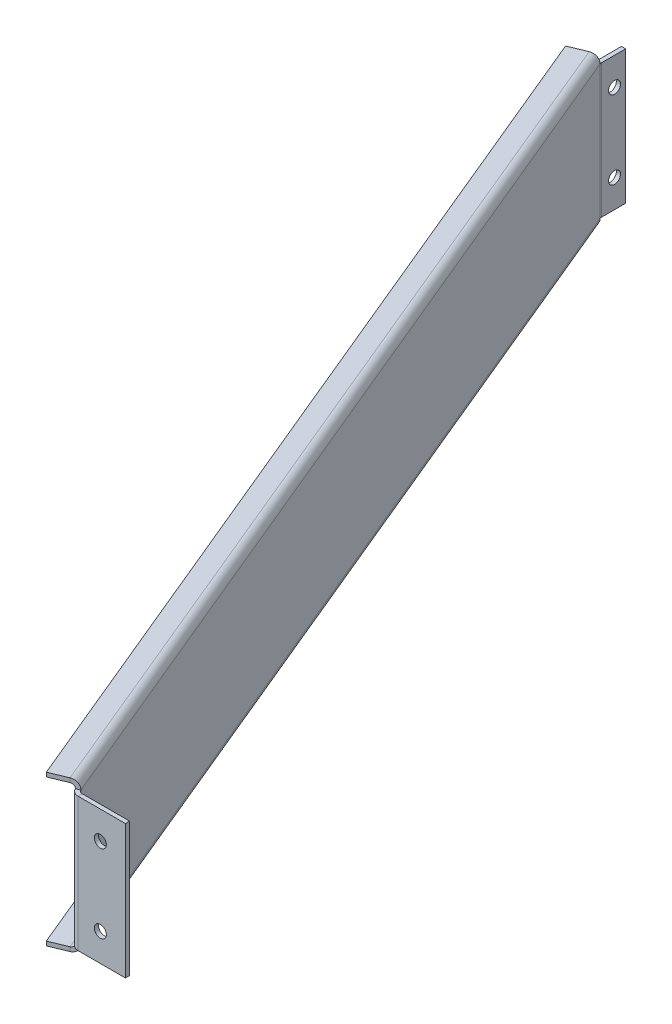
SolidWorks part; units mm, degrees
note: '?' marks a value the reader was unsure of. The reader was unsure of these and kept them because the rebuilt part matched: bend radius of "基体折弯1", "基体折弯2"; flange length of "边线-法兰1".
material "镀铬不锈钢"
ref_plane "前视基准面" through (0, 0, 0) normal (0, 0, 1) x (1, 0, 0)
ref_plane "上视基准面" through (0, 0, 0) normal (0, 1, 0) x (1, 0, 0)
ref_plane "右视基准面" through (0, 0, 0) normal (1, 0, 0) x (0, 0, -1)
ref_axis "基准轴1" through (0, 0, 35.3) along (0, 0, -1)?
sketch "草图1" plane through (0, 0, 0) normal (0, 1, 0) x (1, 0, 0)
  line L0 (63, 329) -> (63, 320)
  line L1 (63, 320) -> (196, 0)
  line L2 (196, 0) -> (214, 0)
  line L3 (0, 0) -> (0, 458.6201) construction
  dimension "D1" = 320
  dimension "D2" = 9
  dimension "D3" = 196
  dimension "D4" = 63
  dimension "D5" = 18
base flange "基体-法兰1" sketch "草图1" end condition mid plane depth 48 reverse direction no thickness 1.5 reverse thickness direction no bend radius 1.5
bend "基体折弯1" bend radius 1.5 bend angle 67.431 parameters "D5"=1
bend "基体折弯2" bend radius 1.5 bend angle 22.569 parameters "D5"=2
edge flange "边线-法兰1" sketch "草图10" flange profiles "草图10", "草图11" flange angle 90 flange length 8 flange position bend outside bend radius 1.5 thickness 1.5 relief rectangular parameters "D6"=10, "D8"=1
sketch "草图10" plane through (165.7443, 24, -68.8875) normal (0, 1, 0) x (-0.3838, 0, -0.9234)
  line L2 (-74.223, 0) -> (-74.223, 8)
  line L3 (-74.223, 8) -> (271.0153, 8)
  line L4 (271.0153, 8) -> (271.0153, 0)
  line L7 (271.0153, 0) -> (-74.223, 0) construction
  line L8 (271.0153, 0) -> (-74.223, 0)
sketch "草图11" plane through (165.7443, -24, -68.8875) normal (0, -1, 0) x (0.3838, 0, 0.9234)
  line L0 (-271.0153, 0) -> (74.223, 0) construction
  line L1 (-271.0153, 0) -> (74.223, 0)
  line L2 (-271.0153, 0) -> (-271.0153, 8)
  line L3 (-271.0153, 8) -> (74.223, 8)
  line L4 (74.223, 8) -> (74.223, 0)
bend "边线折弯1" bend radius 1.5 bend angle 90 parameters "D5"=3
bend "边线折弯2" bend radius 1.5 bend angle 90 parameters "D5"=4
hole_wizard "M4 间隙槽口3" positions "草图13" profile "草图12" hole size "M4" standard "GB" end condition up to next
sketch "草图13" plane through (63, 0, 0) normal (1, 0, 0) x (0, 0, -1)
  line L1 (0, 0) -> (432.2775, 0) construction
  line L2 (-35.3, 0) -> (411.3, 0) construction
  line L4 (329, 24) -> (329, -24) construction
  point P0 (325, 14)
  point P22 (325, -14)
  dimension "D1" = 28
  dimension "D2" = 4
sketch "草图12" plane through (63, 14, -325) normal (0, 1, 0) x (0, 0, -1)
  line L0 (0, 0) -> (0, 1.5)
  line L1 (0, 1.5) -> (2.15, 1.5)
  line L2 (2.15, 1.5) -> (2.15, 0)
  line L5 (2.15, 0) -> (0, 0)
  line L11 (0, -6.35) -> (0, 107.95) construction
  dimension "通孔孔直径" = 4.3
  dimension "通孔孔深度" = 1.5
hole_wizard "M4 间隙槽口4" positions "草图14" profile "草图15" hole size "M4" standard "GB" end condition up to next
sketch "草图14" plane through (0, 0, 0) normal (0, 0, -1) x (-1, 0, 0)
  line L4 (-214, 24) -> (-214, -24) construction
  line L5 (0, 0) -> (71.2451, 0) construction
  point P0 (-205, 14)
  point P22 (-205, -14)
  dimension "D1" = 28
  dimension "D2" = 9
sketch "草图15" plane through (205, 14, 0) normal (1, 0, 0) x (0, 1, 0)
  line L0 (0, 0) -> (0, 1.5)
  line L1 (0, 1.5) -> (2.15, 1.5)
  line L2 (2.15, 1.5) -> (2.15, 0)
  line L5 (2.15, 0) -> (0, 0)
  line L11 (0, -6.35) -> (0, 107.95) construction
  dimension "通孔孔直径" = 4.3
  dimension "通孔孔深度" = 1.5
sketch "折弯-线1" [suppressed] plane through (0, 0, 0) normal (0, 1, 0) x (1, 0, 0)
sketch "边界框1" [suppressed] plane through (0, 0, 0) normal (0, 1, 0) x (1, 0, 0)
sheet metal parameters "钣金6" thickness 1.5 parameters "D1"=3
flat pattern "平板型式6" [suppressed]
sketch "折弯-线2" plane through (173.1601, 0, -68.1733) normal (0.9305, 0, -0.3663) x (-0.3663, 0, -0.9305)
  line L0 (336.4724, 30) -> (336.4724, -30) construction
  line L1 (-72.9718, -30) -> (-72.9718, 30) construction
  line L2 (336.4724, 30) -> (336.4724, -30) construction
  line L3 (-72.9718, -30) -> (-72.9718, 30) construction
sketch3d "边界框2" [suppressed]
  line L0 (10.5492, -60, 0) -> (-423.8749, -60, 0) construction
  line L1 (10.5492, 0, 0) -> (-423.8749, 0, 0) construction
  line L2 (10.5492, -60, 0) -> (10.5492, 0, 0) construction
  line L3 (-423.8749, -60, 0) -> (-423.8749, 0, 0) construction
bend of the flat pattern "展开-<基体折弯1>1"
bend of the flat pattern "展开-<基体折弯2>1"
sheet metal parameters "钣金7" thickness 1.5 parameters "D1"=3
flat pattern "平板型式6"
sketch "折弯-线2" plane through (192.6069, 0, -143.8216) normal (0.8013, 0, -0.5983) x (-0.5983, 0, -0.8013)
  line L0 (200.354, 24) -> (200.354, -24) construction
  line L1 (-178.9437, -24) -> (-178.9437, 24) construction
  line L2 (200.354, 24) -> (200.354, -24) construction
  line L3 (-178.9437, -24) -> (-178.9437, 24) construction
  line L4 (198.9108, -27.5343) -> (-177.5006, -27.5343) construction
  line L5 (-177.5006, 27.5343) -> (198.9108, 27.5343) construction
  line L6 (198.9108, -27.5343) -> (-177.5006, -27.5343) construction
  line L7 (-177.5006, 27.5343) -> (198.9108, 27.5343) construction
sketch3d "边界框2" [suppressed]
  line L0 (10.8933, -65.0686, 0) -> (-393.3012, -65.0686, 0) construction
  line L1 (10.8933, 5.0686, 0) -> (-393.3012, 5.0686, 0) construction
  line L2 (10.8933, -65.0686, 0) -> (10.8933, 5.0686, 0) construction
  line L3 (-393.3012, -65.0686, 0) -> (-393.3012, 5.0686, 0) construction
bend of the flat pattern "展开-<基体折弯1>1"
bend of the flat pattern "展开-<基体折弯2>1"
bend of the flat pattern "展开-<边线折弯1>1"
bend of the flat pattern "展开-<边线折弯2>1"
sheet metal parameters "钣金10" [suppressed] thickness 1.5 parameters "D1"=3
flat pattern "平板型式6"
sketch "折弯-线2" plane through (192.6069, 0, -143.8216) normal (0.8013, 0, -0.5983) x (-0.5983, 0, -0.8013)
  line L0 (200.354, 24) -> (200.354, -24) construction
  line L1 (-178.9437, -24) -> (-178.9437, 24) construction
  line L2 (200.354, 24) -> (200.354, -24) construction
  line L3 (-178.9437, -24) -> (-178.9437, 24) construction
  line L4 (198.9108, -27.5343) -> (-177.5006, -27.5343) construction
  line L5 (-177.5006, 27.5343) -> (198.9108, 27.5343) construction
  line L6 (198.9108, -27.5343) -> (-177.5006, -27.5343) construction
  line L7 (-177.5006, 27.5343) -> (198.9108, 27.5343) construction
sketch3d "边界框2" [suppressed]
  line L0 (10.8933, -65.0686, 0) -> (-393.3012, -65.0686, 0) construction
  line L1 (10.8933, 5.0686, 0) -> (-393.3012, 5.0686, 0) construction
  line L2 (10.8933, -65.0686, 0) -> (10.8933, 5.0686, 0) construction
  line L3 (-393.3012, -65.0686, 0) -> (-393.3012, 5.0686, 0) construction
bend of the flat pattern "展开-<基体折弯1>1"
bend of the flat pattern "展开-<基体折弯2>1"
bend of the flat pattern "展开-<边线折弯1>1"
bend of the flat pattern "展开-<边线折弯2>1"
sheet metal parameters "钣金11" [suppressed] thickness 1.5 parameters "D1"=3
flat pattern "平板型式6"
sketch "折弯-线2" plane through (167.1294, 0, -69.4631) normal (0.9234, 0, -0.3838) x (-0.3838, 0, -0.9234)
  line L0 (271.6023, 24) -> (271.6023, -24) construction
  line L1 (-75.87, -24) -> (-75.87, 24) construction
  line L2 (271.6023, 24) -> (271.6023, -24) construction
  line L3 (-75.87, -24) -> (-75.87, 24) construction
  line L4 (270.716, -27.5343) -> (-73.222, -27.5343) construction
  line L5 (-73.222, 27.5343) -> (270.716, 27.5343) construction
  line L6 (270.716, -27.5343) -> (-73.222, -27.5343) construction
  line L7 (-73.222, 27.5343) -> (270.716, 27.5343) construction
sketch3d "边界框2" [suppressed]
  line L0 (9.5753, -59.0686, 0) -> (-365.8308, -59.0686, 0) construction
  line L1 (9.5753, 11.0686, 0) -> (-365.8308, 11.0686, 0) construction
  line L2 (9.5753, -59.0686, 0) -> (9.5753, 11.0686, 0) construction
  line L3 (-365.8308, -59.0686, 0) -> (-365.8308, 11.0686, 0) construction
bend of the flat pattern "展开-<基体折弯1>1"
bend of the flat pattern "展开-<基体折弯2>1"
bend of the flat pattern "展开-<边线折弯1>1"
bend of the flat pattern "展开-<边线折弯2>1"
